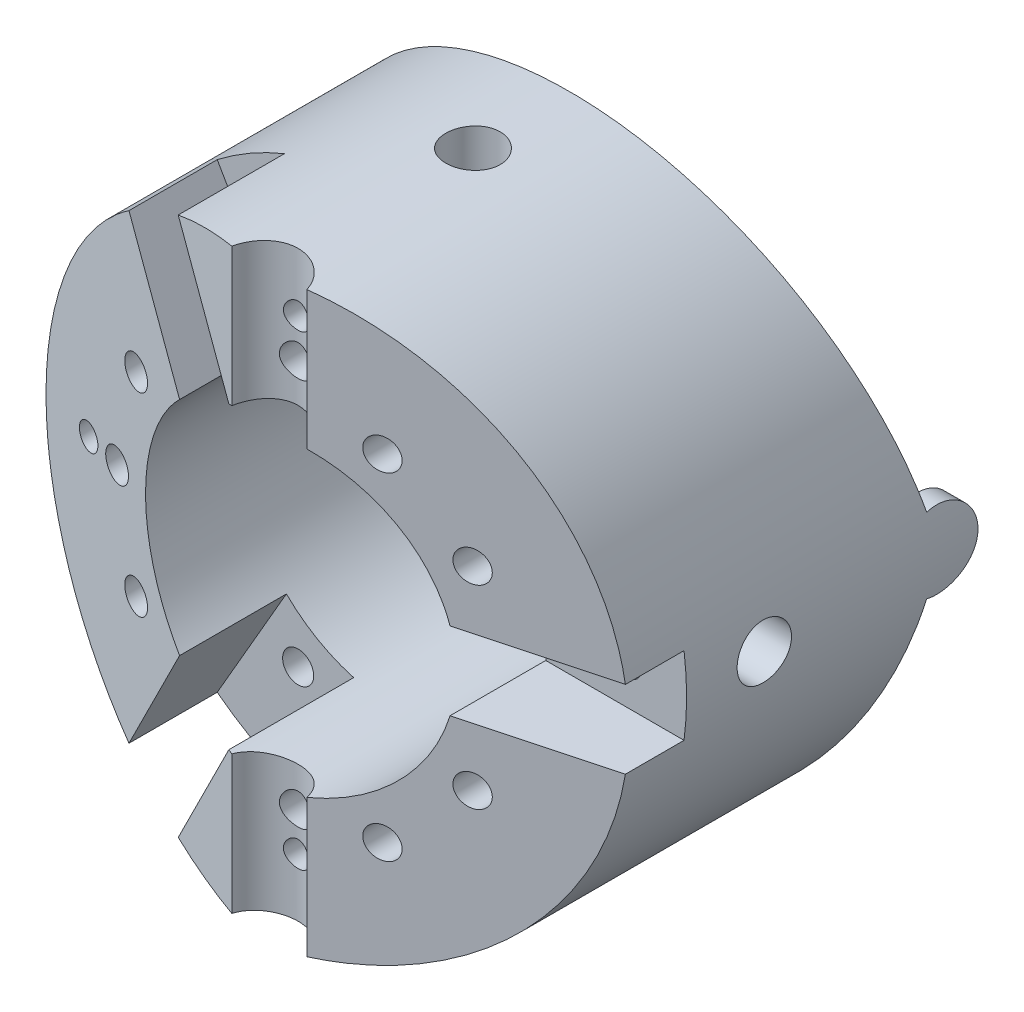
SolidWorks part; units mm, degrees
ref_plane "前视基准面" through (0, 0, 0) normal (0, 0, 1) x (1, 0, 0)
ref_plane "上视基准面" through (0, 0, 0) normal (0, 1, 0) x (1, 0, 0)
ref_plane "右视基准面" through (0, 0, 0) normal (1, 0, 0) x (0, 0, -1)
sketch "草图1" plane through (0, 0, 0) normal (0, 0, 1) x (1, 0, 0)
  circle A0 centre (0, 0) radius 7.5
  dimension "D1" = 15
extrude "凸台-拉伸1" add sketch "草图1" along normal blind 10
sketch "草图2" plane through (0, 0, 0) normal (1, 0, 0) x (0, 0, -1)
  line L0 (0, 0) -> (-2.0096, 7.5)
  line L1 (0, 7.5) -> (-10, 7.5) construction
  line L2 (-2.0096, 7.5) -> (0, 7.5)
  line L3 (0, 7.5) -> (0, 0)
  line L4 (0, 0) -> (-2.0096, -7.5)
  line L5 (-10, -7.5) -> (0, -7.5) construction
  line L6 (-2.0096, -7.5) -> (0, -7.5)
  line L7 (0, -7.5) -> (0, 0)
  dimension "D1" = 15
  dimension "D2" = 15
extrude "切除-拉伸1" cut sketch "草图2" against normal through all and the other way through all contours L3 L2 L0 | L6 L7 L4 region at (0, 5, 0.6699) region at (0, -5, 0.6699)
sketch "草图3" plane through (0, 0, 0) normal (0, 1, 0) x (1, 0, 0)
  line L0 (0, 0) -> (0, -10) construction
  line L1 (-7.5, -10) -> (7.5, -10) construction
  line L2 (0, -10) -> (7.5, -10)
  line L3 (7.5, -10) -> (7.5, -7.9904)
  line L4 (7.5, -7.9904) -> (0, -10)
  line L5 (0, -10) -> (-7.5, -7.9904)
  line L6 (-7.5, 0) -> (-7.5, -10) construction
  line L7 (-7.5, -7.9904) -> (-7.5, -10)
  line L8 (-7.5, -10) -> (0, -10)
  dimension "D1" = 15
  dimension "D2" = 15
extrude "切除-拉伸2" cut sketch "草图3" against normal through all and the other way through all contours L3 L4 L2 | L7 L8 L5 region at (5, 0, 9.3301) region at (-5, 0, 9.3301)
sketch "草图6" plane through (0, 0, 0) normal (1, 0, 0) x (0, 0, -1)
  circle A0 centre (0, 0) radius 1
  dimension "D1" = 2
extrude "凸台-拉伸2" add sketch "草图6" against normal up to surface and the other way up to surface up to face at (0, 0, 7.9904) other way up to face at (0, 0, 7.9904)
sketch "草图7" plane through (0, 0, 0) normal (0, 1, 0) x (1, 0, 0)
  circle A0 centre (0, -10) radius 1
  dimension "D1" = 2
extrude "切除-拉伸7" cut sketch "草图7" against normal through all and the other way through all
sketch "草图8" plane through (0, 0, 0) normal (0, 0, 1) x (1, 0, 0)
  circle A0 centre (0, 0) radius 4
  dimension "D1" = 8
extrude "切除-拉伸9" cut sketch "草图8" against normal through all and the other way through all
sketch "草图9" plane through (0, 0, 0) normal (0, 0, 1) x (1, 0, 0)
  line L0 (0, 0) -> (-5, 0) construction
  circle A0 centre (0, 0) radius 5 construction
  circle A1 centre (-5, 0) radius 0.4
  circle A2 centre (-4.3301, 2.5) radius 0.4
  circle A3 centre (-2.5, 4.3301) radius 0.4
  circle A4 centre (0, 5) radius 0.4
  circle A5 centre (2.5, 4.3301) radius 0.4
  circle A6 centre (4.3301, 2.5) radius 0.4
  circle A7 centre (5, 0) radius 0.4
  circle A8 centre (4.3301, -2.5) radius 0.4
  circle A9 centre (2.5, -4.3301) radius 0.4
  circle A10 centre (0, -5) radius 0.4
  circle A11 centre (-2.5, -4.3301) radius 0.4
  circle A12 centre (-4.3301, -2.5) radius 0.4
  point P29 (0, 0)
  dimension "D1" = 10
  dimension "D2" = 0.8
  dimension "D3" = 12
extrude "切除-拉伸10" cut sketch "草图9" against normal through all and the other way through all
sketch "草图10" plane through (0, 0, 0) normal (0, 0, 1) x (1, 0, 0)
  line L0 (0, 0) -> (-6, 0) construction
  circle A0 centre (0, 0) radius 6 construction
  circle A1 centre (-6, 0) radius 0.325
  circle A2 centre (0, 6) radius 0.325
  circle A3 centre (6, 0) radius 0.325
  circle A4 centre (0, -6) radius 0.325
  point P14 (0, 0)
  dimension "D1" = 12
  dimension "D2" = 0.65
  dimension "D3" = 4
extrude "切除-拉伸11" cut sketch "草图10" against normal through all and the other way through all
ref_plane "基准面1" through (0, 0, -1) normal (0, 0, -1) x (-1, 0, 0)
sketch "草图11" plane through (0, 0, -1) normal (0, 0, -1) x (-1, 0, 0)
  line L0 (-5.6596, -0.9659) -> (-5.6596, 0.9659) construction
  line L1 (-3.8816, -0.9659) -> (-7.4375, -0.9659) construction
  line L2 (-7.433, -1) -> (-3.873, -1) construction
  line L3 (-4.4096, -1) -> (-6.9096, -1)
  line L4 (-4.4096, -1) -> (-4.4096, 1)
  line L5 (-4.4096, 1) -> (-6.9096, 1)
  line L6 (-6.9096, -1) -> (-6.9096, 1)
  line L7 (-4.4096, -1) -> (-6.9096, 1) construction
  line L8 (-4.4096, 1) -> (-6.9096, -1) construction
  line L9 (-3.873, 1) -> (-7.433, 1) construction
  line L10 (0, 0) -> (0, 7.5) construction
  line L11 (4.4096, -1) -> (6.9096, -1)
  line L12 (6.9096, -1) -> (6.9096, 1)
  line L13 (4.4096, 1) -> (6.9096, 1)
  line L14 (4.4096, -1) -> (4.4096, 1)
  arc A0 (7.4375, 0.9659) -> (-7.4375, 0.9659) centre (0, 0) ccw construction
  point P4 (-5.6596, 0)
  dimension "D1" = 2.5
extrude "切除-拉伸12" cut sketch "草图11" against normal blind 1
ref_plane "基准面2" through (0, -7.5, 0) normal (0, -1, 0) x (-1, 0, 0)
sketch "草图12" plane through (0, -7.5, 0) normal (0, -1, 0) x (-1, 0, 0)
  line L0 (0, -9) -> (0, -2.0096) construction
  arc A0 (0.9659, -9.7412) -> (-0.9659, -9.7412) centre (0, -10) ccw construction
  circle A1 centre (0, -4.5) radius 0.7
  ellipse E0 centre (0, 0) end of major axis (-7.5, 0) minor radius 2.0096 (-7.4375, -0.2588) -> (7.4375, -0.2588) ccw construction
  point P15 (0, -5.5048)
  point P16 (0, 0)
  point P17 (0, -4.5208)
  dimension "D1" = 1.4
  dimension "D2" = 4.5
extrude "切除-拉伸13" cut sketch "草图12" against normal blind 1.5
pattern_circular "阵列(圆周)1" count 4 over 360 about axis through (0, 0, 10) along (0, 0, -1) of "切除-拉伸13"
ref_plane "基准面3" through (0, 0, 10) normal (0, 0, 1) x (1, 0, 0)
sketch "草图15" plane through (0, 0, 10) normal (0, 0, 1) x (1, 0, 0)
  line L0 (0, 0) -> (7.5, 0) construction
  line L2 (0.7856, 1) -> (8.0925, 1)
  line L3 (0.7856, 1) -> (0.7856, -1)
  line L4 (0.7856, -1) -> (8.0925, -1)
  line L5 (8.0925, 1) -> (8.0925, -1)
  line L6 (0.7856, 1) -> (8.0925, -1) construction
  line L7 (0.7856, -1) -> (8.0925, 1) construction
  arc A0 (0.9659, -7.4375) -> (0.9659, 7.4375) centre (0, 0) ccw construction
  point P6 (4.439, 0)
  dimension "D1" = 2
extrude "切除-拉伸14" cut sketch "草图15" against normal blind 3.5
pattern_circular "阵列(圆周)2" count 3 over 360 about axis through (0, 0, 10) along (0, 0, -1) of "切除-拉伸14"
